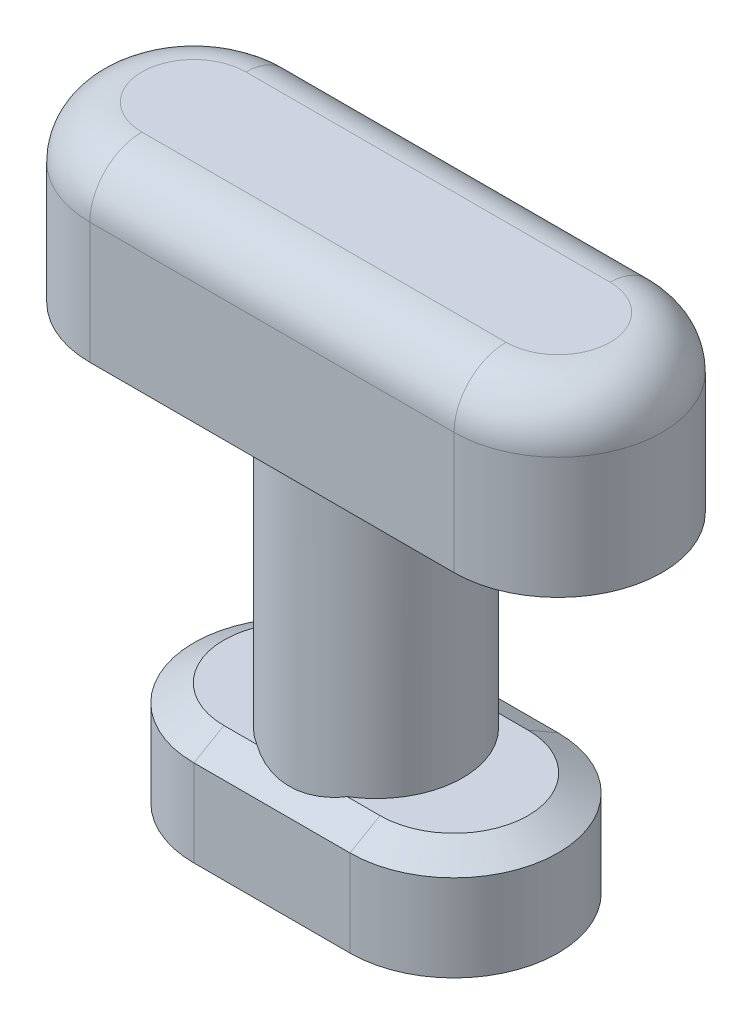
SolidWorks part; units mm, degrees
ref_plane "Front Plane" through (0, 0, 0) normal (0, 0, 1) x (1, 0, 0)
ref_plane "Top Plane" through (0, 0, 0) normal (0, 1, 0) x (1, 0, 0)
ref_plane "Right Plane" through (0, 0, 0) normal (1, 0, 0) x (0, 0, -1)
sketch "Sketch1" plane through (0, 0, 0) normal (0, 1, 0) x (1, 0, 0)
  line L0 (-2.25, 0) -> (2.25, 0) construction
  line L1 (-2.25, 3) -> (2.25, 3)
  line L2 (-2.25, -3) -> (2.25, -3)
  circle A0 centre (0, 0) radius 2.5
  arc A1 (-2.25, 3) -> (-2.25, -3) centre (-2.25, 0) ccw
  arc A2 (2.25, -3) -> (2.25, 3) centre (2.25, 0) ccw
  point P5 (0, 0)
  point P10 (0, 0)
  dimension "D1" = 5
  dimension "D2" = 6
  dimension "D3" = 4.5
extrude "Boss-Extrude1" add sketch "Sketch1" along normal blind 3 contours A0 | L2 A2 L1 A1 A0 region at (0, 0, -2.8791) region at (0, 0, 0)
extrude "Boss-Extrude2" add sketch "Sketch1<3>" along normal blind 11 contours A0 region at (0, 0, 0)
sketch "Sketch1<3>" plane through (0, 0, 0) normal (0, 1, 0) x (1, 0, 0) same geometry as "Sketch1"
sketch "Sketch2" plane through (0, 11, 0) normal (0, 1, 0) x (1, 0, 0)
  line L0 (-5.25, 0) -> (5.25, 0) construction
  line L1 (-5.25, 3) -> (5.25, 3)
  line L2 (-5.25, -3) -> (5.25, -3)
  arc A0 (-2.25, 3) -> (-2.25, -3) centre (-2.25, 0) ccw construction
  arc A1 (2.25, -3) -> (2.25, 3) centre (2.25, 0) ccw construction
  arc A2 (-5.25, 3) -> (-5.25, -3) centre (-5.25, 0) ccw
  arc A3 (5.25, -3) -> (5.25, 3) centre (5.25, 0) ccw
  point P8 (0, 0)
  dimension "D1" = 6
extrude "Boss-Extrude3" add sketch "Sketch2" along normal blind 5
chamfer "Chamfer1" distance 0.5 angle 60 4 edges at (-5.25, 3, 0) (0, 3, -3) (5.25, 3, 0) (0, 3, 3) first distance on face at (-3.75, 1.5, 0) first distance on face at (0, 1.5, -3) first distance on face at (3.75, 1.5, 0) first distance on face at (0, 1.5, 3)
fillet "Fillet1" radius 1.5 4 edges at (0, 16, -3) (8.25, 16, 0) (0, 16, 3) (-8.25, 16, 0)
equation "\"0.5.00mm\"=2"
